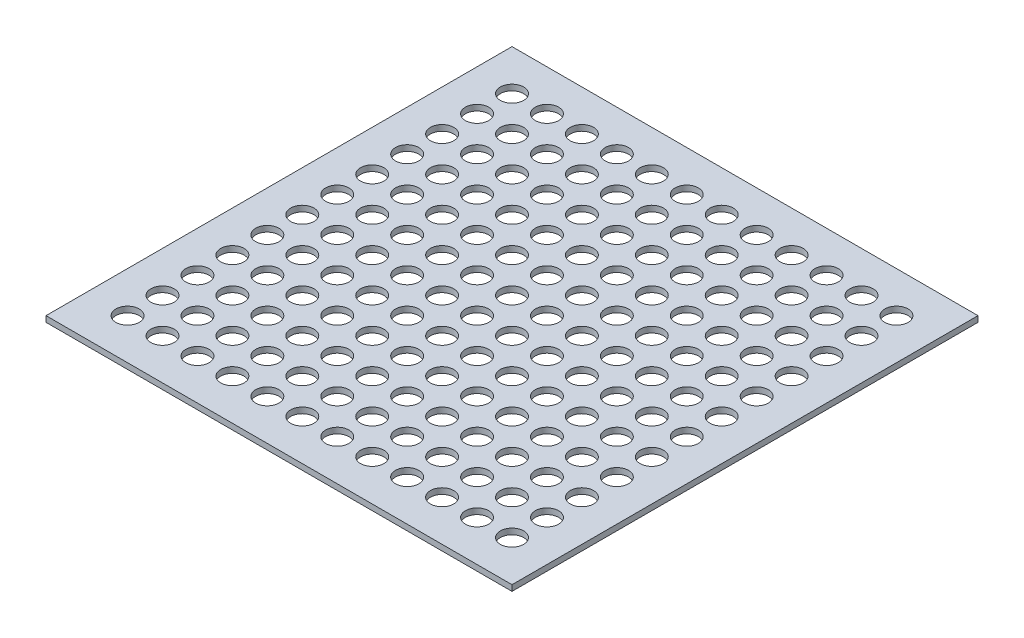
SolidWorks part; units mm, degrees
ref_plane "Front Plane" through (0, 0, 0) normal (0, 0, 1) x (1, 0, 0)
ref_plane "Top Plane" through (0, 0, 0) normal (0, 1, 0) x (1, 0, 0)
ref_plane "Right Plane" through (0, 0, 0) normal (1, 0, 0) x (0, 0, -1)
sketch "Sketch1" plane through (0, 0, 0) normal (0, 1, 0) x (1, 0, 0)
  line L1 (0, 400) -> (400, 400)
  line L2 (0, 400) -> (0, 0)
  line L3 (0, 0) -> (400, 0)
  line L4 (400, 400) -> (400, 0)
  circle A1 centre (35, 35) radius 10
  circle A2 centre (65, 35) radius 10
  circle A3 centre (95, 35) radius 10
  circle A4 centre (125, 35) radius 10
  circle A5 centre (155, 35) radius 10
  circle A6 centre (185, 35) radius 10
  circle A7 centre (215, 35) radius 10
  circle A8 centre (245, 35) radius 10
  circle A9 centre (275, 35) radius 10
  circle A10 centre (305, 35) radius 10
  circle A11 centre (335, 35) radius 10
  circle A12 centre (365, 35) radius 10
  circle A13 centre (65, 65) radius 10
  circle A14 centre (95, 65) radius 10
  circle A15 centre (125, 65) radius 10
  circle A16 centre (155, 65) radius 10
  circle A17 centre (185, 65) radius 10
  circle A18 centre (215, 65) radius 10
  circle A19 centre (245, 65) radius 10
  circle A20 centre (275, 65) radius 10
  circle A21 centre (305, 65) radius 10
  circle A22 centre (335, 65) radius 10
  circle A23 centre (365, 65) radius 10
  circle A24 centre (65, 95) radius 10
  circle A25 centre (95, 95) radius 10
  circle A26 centre (125, 95) radius 10
  circle A27 centre (155, 95) radius 10
  circle A28 centre (185, 95) radius 10
  circle A29 centre (215, 95) radius 10
  circle A30 centre (245, 95) radius 10
  circle A31 centre (275, 95) radius 10
  circle A32 centre (305, 95) radius 10
  circle A33 centre (335, 95) radius 10
  circle A34 centre (365, 95) radius 10
  circle A35 centre (65, 125) radius 10
  circle A36 centre (95, 125) radius 10
  circle A37 centre (125, 125) radius 10
  circle A38 centre (155, 125) radius 10
  circle A39 centre (185, 125) radius 10
  circle A40 centre (215, 125) radius 10
  circle A41 centre (245, 125) radius 10
  circle A42 centre (275, 125) radius 10
  circle A43 centre (305, 125) radius 10
  circle A44 centre (335, 125) radius 10
  circle A45 centre (365, 125) radius 10
  circle A46 centre (65, 155) radius 10
  circle A47 centre (95, 155) radius 10
  circle A48 centre (125, 155) radius 10
  circle A49 centre (155, 155) radius 10
  circle A50 centre (185, 155) radius 10
  circle A51 centre (215, 155) radius 10
  circle A52 centre (245, 155) radius 10
  circle A53 centre (275, 155) radius 10
  circle A54 centre (305, 155) radius 10
  circle A55 centre (335, 155) radius 10
  circle A56 centre (365, 155) radius 10
  circle A57 centre (65, 185) radius 10
  circle A58 centre (95, 185) radius 10
  circle A59 centre (125, 185) radius 10
  circle A60 centre (155, 185) radius 10
  circle A61 centre (185, 185) radius 10
  circle A62 centre (215, 185) radius 10
  circle A63 centre (245, 185) radius 10
  circle A64 centre (275, 185) radius 10
  circle A65 centre (305, 185) radius 10
  circle A66 centre (335, 185) radius 10
  circle A67 centre (365, 185) radius 10
  circle A68 centre (65, 215) radius 10
  circle A69 centre (95, 215) radius 10
  circle A70 centre (125, 215) radius 10
  circle A71 centre (155, 215) radius 10
  circle A72 centre (185, 215) radius 10
  circle A73 centre (215, 215) radius 10
  circle A74 centre (245, 215) radius 10
  circle A75 centre (275, 215) radius 10
  circle A76 centre (305, 215) radius 10
  circle A77 centre (335, 215) radius 10
  circle A78 centre (365, 215) radius 10
  circle A79 centre (65, 245) radius 10
  circle A80 centre (95, 245) radius 10
  circle A81 centre (125, 245) radius 10
  circle A82 centre (155, 245) radius 10
  circle A83 centre (185, 245) radius 10
  circle A84 centre (215, 245) radius 10
  circle A85 centre (245, 245) radius 10
  circle A86 centre (275, 245) radius 10
  circle A87 centre (305, 245) radius 10
  circle A88 centre (335, 245) radius 10
  circle A89 centre (365, 245) radius 10
  circle A90 centre (65, 275) radius 10
  circle A91 centre (95, 275) radius 10
  circle A92 centre (125, 275) radius 10
  circle A93 centre (155, 275) radius 10
  circle A94 centre (185, 275) radius 10
  circle A95 centre (215, 275) radius 10
  circle A96 centre (245, 275) radius 10
  circle A97 centre (275, 275) radius 10
  circle A98 centre (305, 275) radius 10
  circle A99 centre (335, 275) radius 10
  circle A100 centre (365, 275) radius 10
  circle A101 centre (65, 305) radius 10
  circle A102 centre (95, 305) radius 10
  circle A103 centre (125, 305) radius 10
  circle A104 centre (155, 305) radius 10
  circle A105 centre (185, 305) radius 10
  circle A106 centre (215, 305) radius 10
  circle A107 centre (245, 305) radius 10
  circle A108 centre (275, 305) radius 10
  circle A109 centre (305, 305) radius 10
  circle A110 centre (335, 305) radius 10
  circle A111 centre (365, 305) radius 10
  circle A112 centre (65, 335) radius 10
  circle A113 centre (95, 335) radius 10
  circle A114 centre (125, 335) radius 10
  circle A115 centre (155, 335) radius 10
  circle A116 centre (185, 335) radius 10
  circle A117 centre (215, 335) radius 10
  circle A118 centre (245, 335) radius 10
  circle A119 centre (275, 335) radius 10
  circle A120 centre (305, 335) radius 10
  circle A121 centre (335, 335) radius 10
  circle A122 centre (365, 335) radius 10
  circle A123 centre (65, 365) radius 10
  circle A124 centre (95, 365) radius 10
  circle A125 centre (125, 365) radius 10
  circle A126 centre (155, 365) radius 10
  circle A127 centre (185, 365) radius 10
  circle A128 centre (215, 365) radius 10
  circle A129 centre (245, 365) radius 10
  circle A130 centre (275, 365) radius 10
  circle A131 centre (305, 365) radius 10
  circle A132 centre (335, 365) radius 10
  circle A133 centre (365, 365) radius 10
  circle A134 centre (35, 65) radius 10
  circle A135 centre (35, 95) radius 10
  circle A136 centre (35, 125) radius 10
  circle A137 centre (35, 155) radius 10
  circle A138 centre (35, 185) radius 10
  circle A139 centre (35, 215) radius 10
  circle A140 centre (35, 245) radius 10
  circle A141 centre (35, 275) radius 10
  circle A142 centre (35, 305) radius 10
  circle A143 centre (35, 335) radius 10
  circle A144 centre (35, 365) radius 10
  point P7 (35, 35)
  dimension "D4" = 20
  dimension "D1" = 400
  dimension "D2" = 35
  dimension "D3" = 35
  dimension "D5" = 12
  dimension "D6" = 12
extrude "Boss-Extrude1" add sketch "Sketch1" along normal blind 5 contours L4 L1 L2 L3 region at (200, 0, -200)
